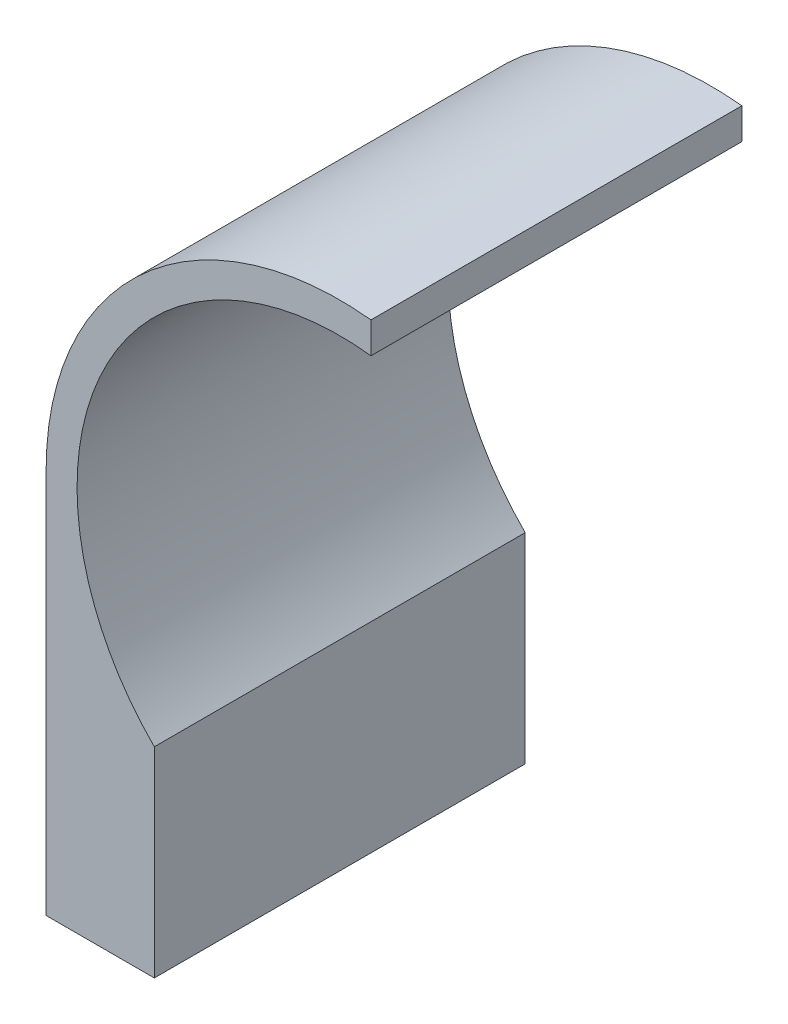
SolidWorks part; units mm, degrees
material "201 Annealed Stainless Steel (SS)"
ref_plane "Front Plane" through (0, 0, 0) normal (0, 0, 1) x (1, 0, 0)
ref_plane "Top Plane" through (0, 0, 0) normal (0, 1, 0) x (1, 0, 0)
ref_plane "Right Plane" through (0, 0, 0) normal (1, 0, 0) x (0, 0, -1)
sketch "Sketch1" plane through (0, 0, 0) normal (0, 0, 1) x (1, 0, 0)
  line L0 (0, 0) -> (0, -95) construction
  line L1 (-60, -60.208) -> (-60, -125)
  line L2 (0, 0) -> (101.5936, 0) construction
  line L3 (10.1, 111.7322) -> (10.1, -25.0367) construction
  line L5 (10.1, 94.4616) -> (10.1, 84.3978)
  line L7 (0, 0) -> (-138.7196, 0) construction
  line L8 (-95, 0) -> (-95, -125)
  line L9 (-60, -125) -> (-95, -125)
  line L10 (0, -95) -> (0, -125) construction
  line L11 (0, -125) -> (-120, -125) construction
  line L12 (-60, -60.208) -> (60, -60.208) construction
  line L13 (0, -85) -> (-60, -85) construction
  circle A0 centre (0, 0) radius 85 construction
  circle A1 centre (0, 0) radius 95 construction
  arc A2 (-60, -60.208) -> (10.1, 84.3978) centre (0, 0) cw
  arc A3 (-95, 0) -> (10.1, 94.4616) centre (0, 0) cw
  point P4 (-60, -85)
  dimension "D1" = 170
  dimension "D2" = 190
  dimension "D6" = 95
  dimension "D5" = 30
  dimension "D4" = 10.1
  dimension "D7" = 120
extrude "Inner Ring - Left Side" add sketch "Sketch1" along normal blind 120
sketch "Sketch2" plane through (-60, 0, 0) normal (1, 0, 0) x (0, 0, -1)
  line L0 (0, -85) -> (-120, -85) construction
  line L1 (-120, -125) -> (-120, -60.208) construction
